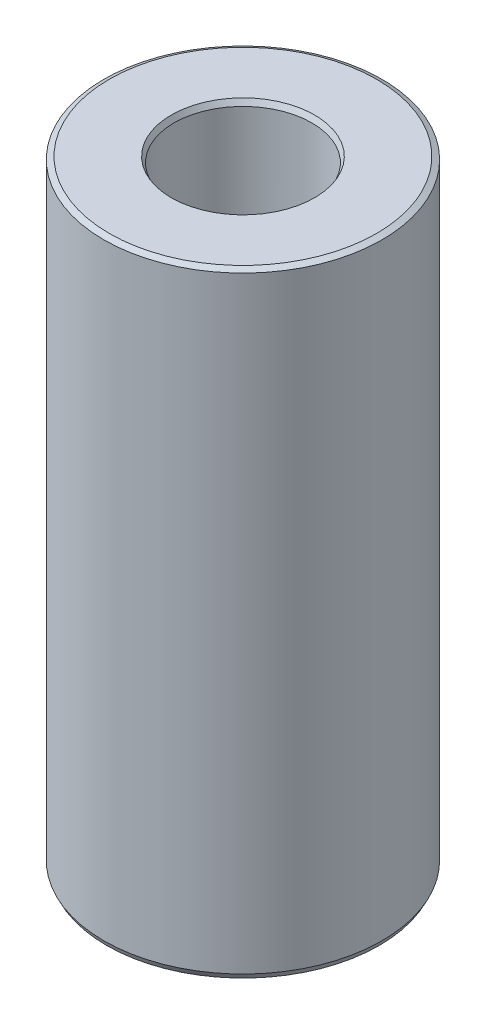
SolidWorks part; units mm, degrees
ref_plane "Front Plane" through (0, 0, 0) normal (0, 0, 1) x (1, 0, 0)
ref_plane "Top Plane" through (0, 0, 0) normal (0, 1, 0) x (1, 0, 0)
ref_plane "Right Plane" through (0, 0, 0) normal (1, 0, 0) x (0, 0, -1)
sketch "Sketch1" plane through (0, 0, 0) normal (0, 1, 0) x (1, 0, 0)
  circle A0 centre (0, 0) radius 42.5
  dimension "SLEEVE_OD" = 85
extrude "Boss-Extrude1" add sketch "Sketch1" along normal blind 188.0231
sketch "Sketch2" plane through (0, 0, 0) normal (0, 1, 0) x (1, 0, 0)
  circle A0 centre (0, 0) radius 21.0653
  dimension "BORE_D" = 42.1305
extrude "Cut-Extrude1" cut sketch "Sketch2" along normal through all
chamfer "Chamfer1" distance 0.8436 angle 63.191 4 edges at (0, 188.0231, 21.0653) (0, 0, 21.0653) (0, 0, 42.5) (0, 188.0231, 42.5) first distance on face at (0, 188.0231, 21.0653) first distance on face at (0, 0, 21.0653) first distance on face at (0, 188.0231, 42.5)
